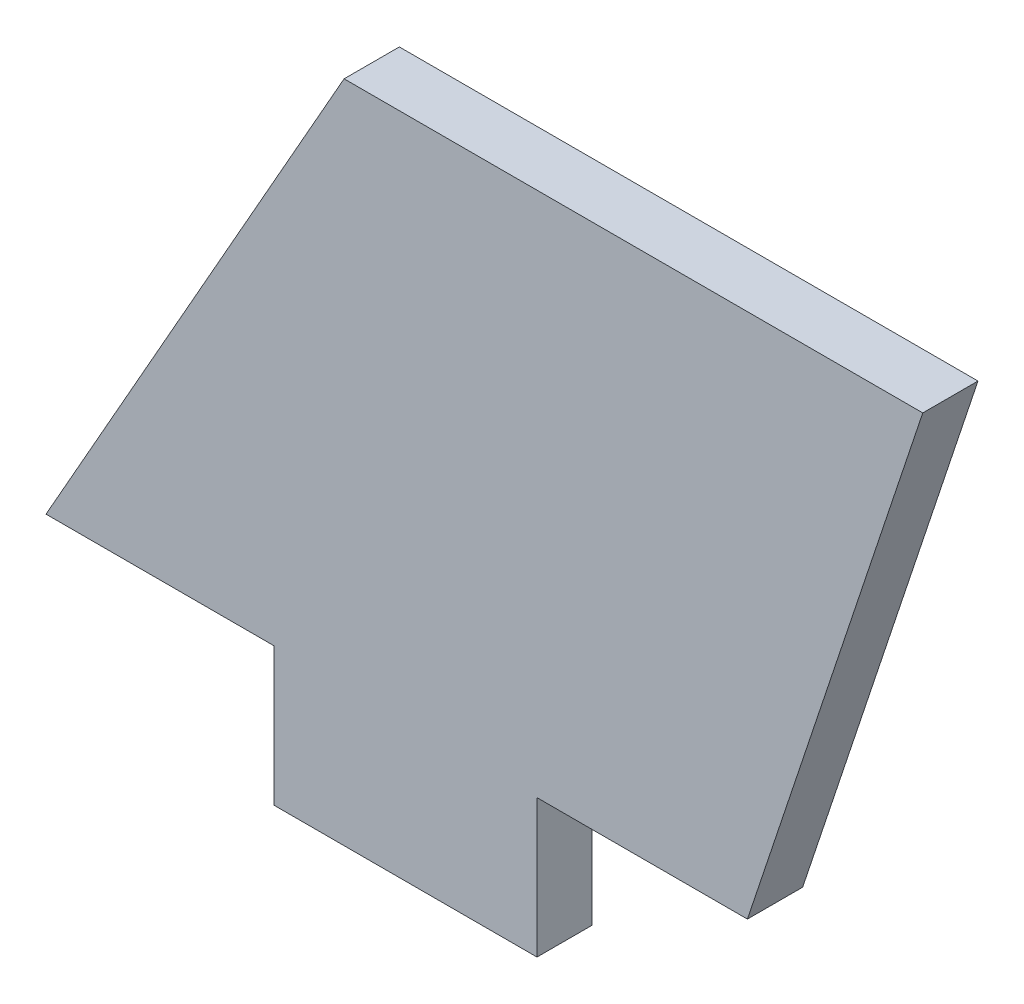
SolidWorks part; units mm, degrees
ref_plane "Front Plane" through (0, 0, 0) normal (0, 0, 1) x (1, 0, 0)
ref_plane "Top Plane" through (0, 0, 0) normal (0, 1, 0) x (1, 0, 0)
ref_plane "Right Plane" through (0, 0, 0) normal (1, 0, 0) x (0, 0, -1)
sketch "Sketch1" plane through (0, 0, 0) normal (0, 0, 1) x (1, 0, 0)
  line L0 (0, 0) -> (13, 0)
  line L1 (13, 0) -> (13, -7.875)
  line L2 (13, -7.875) -> (28, -7.875)
  line L3 (28, -7.875) -> (28, 0)
  line L4 (28, 0) -> (40, 0)
  line L5 (40, 0) -> (50, 30)
  line L6 (50, 30) -> (17, 30)
  line L7 (17, 30) -> (0, 0)
  dimension "D1" = 40
  dimension "D2" = 7.875
  dimension "D3" = 15
  dimension "D4" = 17
  dimension "D5" = 33
  dimension "D6" = 12
  dimension "D7" = 30
extrude "Boss-Extrude1" add sketch "Sketch1" along normal blind 3.1496
